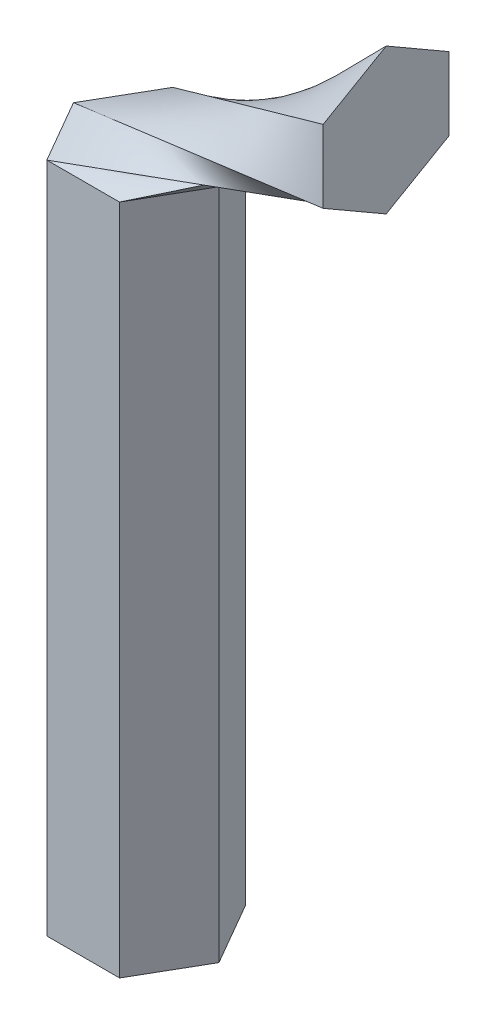
SolidWorks part; units mm, degrees
ref_plane "Front Plane" through (0, 0, 0) normal (0, 0, 1) x (1, 0, 0)
ref_plane "Top Plane" through (0, 0, 0) normal (0, 1, 0) x (1, 0, 0)
ref_plane "Right Plane" through (0, 0, 0) normal (1, 0, 0) x (0, 0, -1)
sketch "Sketch1" plane through (0, 0, 0) normal (0, 1, 0) x (1, 0, 0)
  line L1 (7.699, 0) -> (3.8495, 6.6675)
  line L2 (3.8495, 6.6675) -> (-3.8495, 6.6675)
  line L3 (-3.8495, 6.6675) -> (-7.699, 0)
  line L4 (-7.699, 0) -> (-3.8495, -6.6675)
  line L5 (-3.8495, -6.6675) -> (3.8495, -6.6675)
  line L6 (3.8495, -6.6675) -> (7.699, 0)
  circle A0 centre (0, 0) radius 6.6675 construction
  dimension "D1" = 13.335
extrude "Boss-Extrude1" add sketch "Sketch1" along normal mid plane 71.12
sketch "Sketch2" plane through (0, 35.56, 0) normal (0, 1, 0) x (1, 0, 0)
  line L6 (3.8495, -6.6675) -> (7.699, 0)
  line L7 (7.699, 0) -> (3.8495, 6.6675)
  line L8 (3.8495, 6.6675) -> (-3.8495, 6.6675)
  line L9 (-3.8495, 6.6675) -> (-7.699, 0)
  line L10 (-7.699, 0) -> (-3.8495, -6.6675)
  line L11 (-3.8495, -6.6675) -> (3.8495, -6.6675)
  line L12 (3.8495, -6.6675) -> (7.699, 0)
  line L13 (7.699, 0) -> (3.8495, 6.6675)
  line L14 (3.8495, 6.6675) -> (-3.8495, 6.6675)
  line L15 (-3.8495, 6.6675) -> (-7.699, 0)
  line L16 (-7.699, 0) -> (-3.8495, -6.6675)
  line L17 (-3.8495, -6.6675) -> (3.8495, -6.6675)
  dimension "D1" = 0
ref_plane "Plane1" through (25.4, 0, 0) normal (1, 0, 0) x (0, 0, -1)
sketch "Sketch3" plane through (25.4, 0, 0) normal (1, 0, 0) x (0, 0, -1)
  line L0 (-6.6675, 35.56) -> (-6.6675, -35.56) construction
  line L1 (6.6675, 45.7595) -> (6.6675, 53.4584)
  line L2 (6.6675, 53.4584) -> (0, 57.3079)
  line L3 (0, 57.3079) -> (-6.6675, 53.4584)
  line L4 (-6.6675, 53.4584) -> (-6.6675, 45.7595)
  line L5 (-6.6675, 45.7595) -> (0, 41.91)
  line L6 (0, 41.91) -> (6.6675, 45.7595)
  line L7 (6.6675, 35.56) -> (6.6675, -35.56) construction
  circle A0 centre (0, 49.609) radius 6.6675 construction
  point P10 (-2.1682, 33.3238)
  point P13 (0, 35.56)
  point P16 (0, 41.9303)
  dimension "D1" = 6.35
loft "Loft2" add profiles "Sketch3", "Sketch2" connector at (25.4, 45.7595, 6.6675) connector at (-7.699, 35.56, 0)
equation "\"Hex width\"= .525"
equation "\"D1@Sketch1\"=\"Hex width\""
